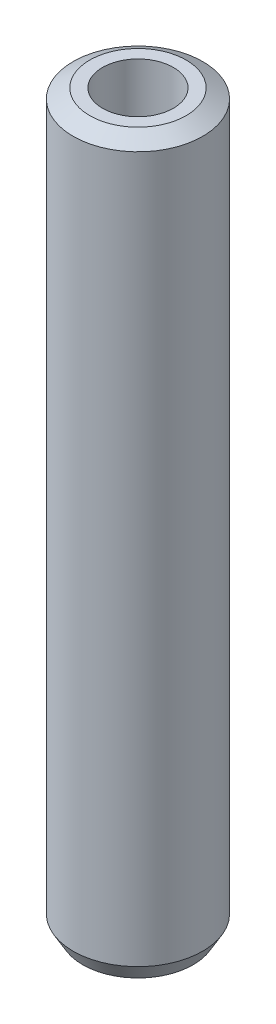
SolidWorks part; units mm, degrees
ref_plane "Front Plane" through (0, 0, 0) normal (0, 0, 1) x (1, 0, 0)
ref_plane "Top Plane" through (0, 0, 0) normal (0, 1, 0) x (1, 0, 0)
ref_plane "Right Plane" through (0, 0, 0) normal (1, 0, 0) x (0, 0, -1)
sketch "Sketch1" plane through (0, 0, 0) normal (0, 1, 0) x (1, 0, 0)
  circle A0 centre (0, 0) radius 22.5
  dimension "SHAFT_OD" = 45
extrude "Boss-Extrude1" add sketch "Sketch1" along normal blind 254.0824
sketch "Sketch2" plane through (0, 0, 0) normal (0, 1, 0) x (1, 0, 0)
  circle A0 centre (0, 0) radius 12.2979
  dimension "BORE_D" = 24.5959
extrude "Cut-Extrude1" cut sketch "Sketch2" along normal through all
chamfer "Chamfer1" distance 3.3276 angle 60 2 edges at (0, 254.0824, 22.5) (0, 0, 22.5) first distance on face at (0, 254.0824, 22.5) first distance on face at (0, 0, 12.2979)
